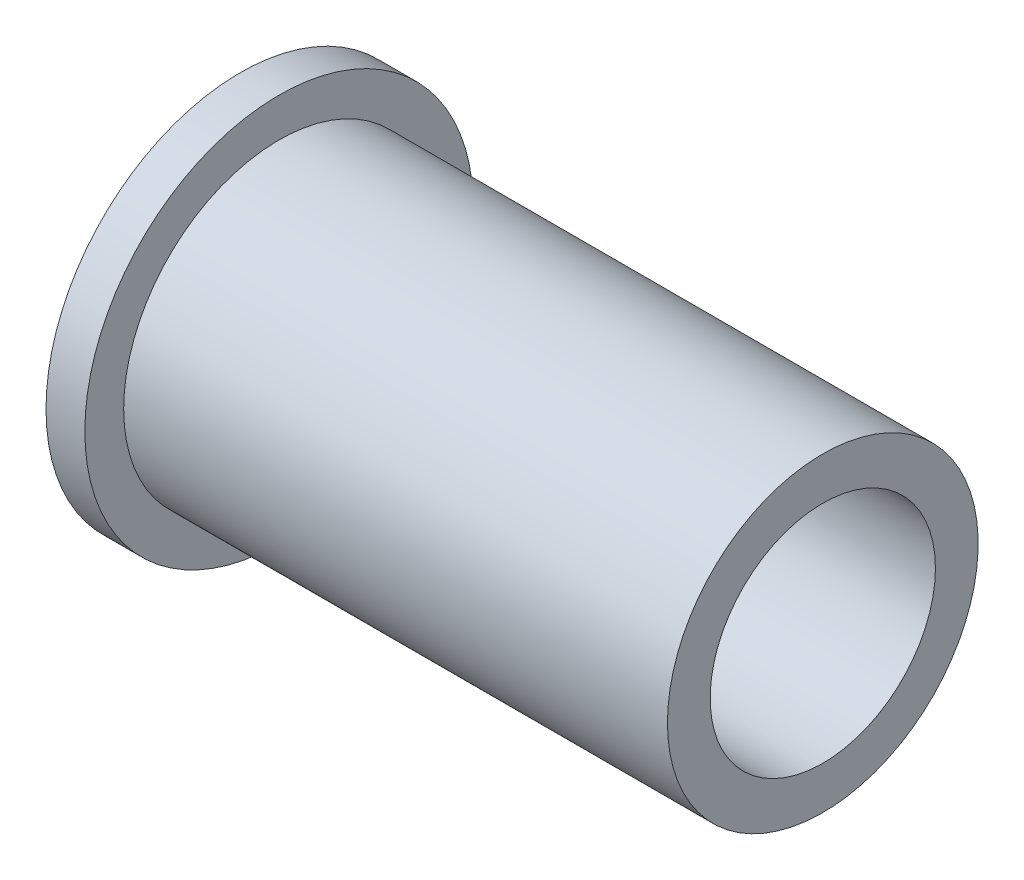
SolidWorks part; units mm, degrees
material "Latão"
ref_plane "Front" through (0, 0, 0) normal (0, 0, 1) x (1, 0, 0)
ref_plane "Top" through (0, 0, 0) normal (0, 1, 0) x (1, 0, 0)
ref_plane "Right" through (0, 0, 0) normal (1, 0, 0) x (0, 0, -1)
sketch "Sketch2" plane through (0, 0, 0) normal (0, 0, 1) x (1, 0, 0)
  line L0 (-33.6191, 0) -> (29.6472, 0) construction
  line L1 (-10, 0) -> (-10, 5)
  line L2 (-10, 5) -> (-9, 5)
  line L3 (-9, 5) -> (-9, 4)
  line L4 (-9, 4) -> (5, 4)
  line L5 (5, 4) -> (5, 0)
  line L6 (-10, 0) -> (5, 0)
  dimension "D1" = 5
  dimension "D2" = 15
  dimension "D3" = 14
  dimension "D4" = 5
  dimension "D5" = 4
revolve "Revolve1" add sketch "Sketch2" angle 360 about L0
hole_wizard "Furo com folga de M51" positions "Esboço3" profile "Esboço2" hole size "M5" standard "ISO"
sketch "Esboço3" plane through (5, 0, 0) normal (1, 0, 0) x (0, 0, -1)
  circle A0 centre (0, 0) radius 4 construction
  point P0 (0, 0)
sketch "Esboço2" plane through (5, 0, 0) normal (0, 1, 0) x (0, 0, -1)
  line L0 (0, 0) -> (0, 7.1717)
  line L1 (0, 7.1717) -> (2.9, 6)
  line L2 (2.9, 6) -> (2.9, 0)
  line L5 (2.9, 0) -> (0, 0)
  line L10 (0, 7.1717) -> (-2.9, 6) construction
  line L11 (0, -6.35) -> (0, 107.95) construction
  dimension "Hole Dia." = 5.8
  dimension "Hole Depth" = 6
  dimension "Drill Angle" = 136
dome "Domo1" faces to dome 1 distance 0.5 reverse direction no elliptical dome no face at (-10, 0, 5) parameters "D1"=0.5
